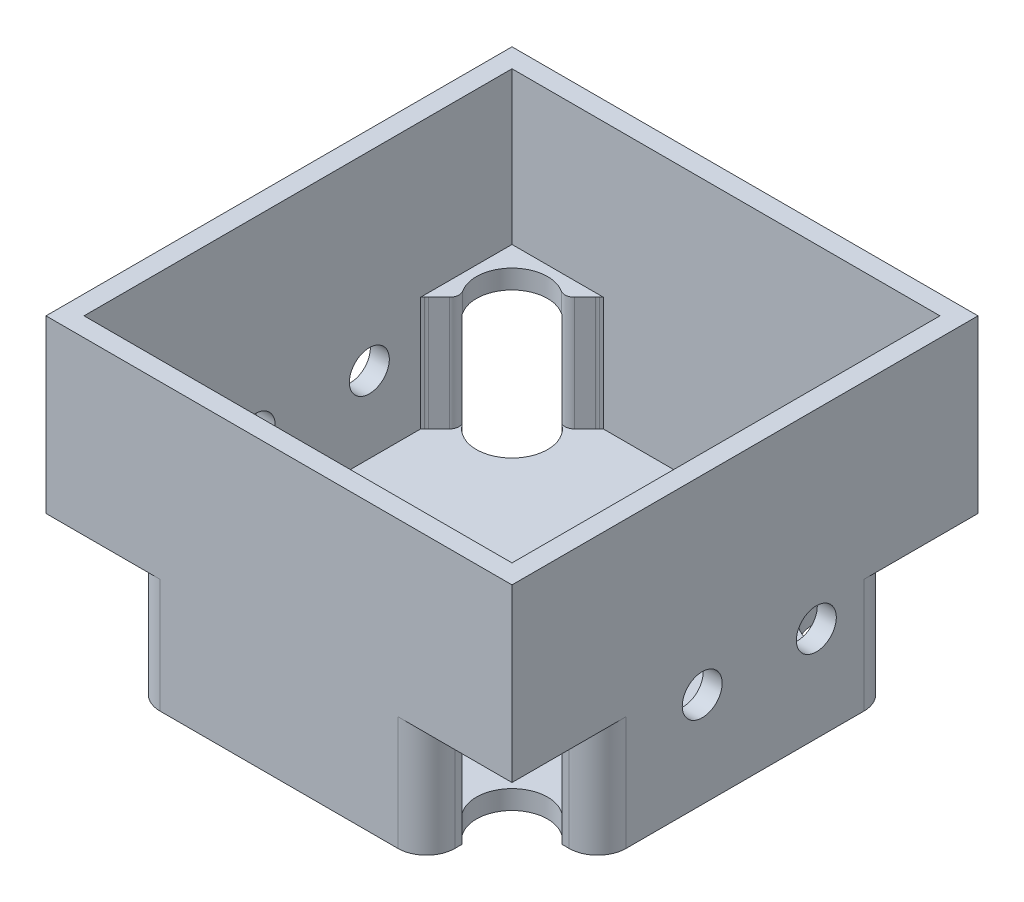
SolidWorks part; units mm, degrees
ref_plane "前视基准面" through (0, 0, 0) normal (0, 0, 1) x (1, 0, 0)
ref_plane "上视基准面" through (0, 0, 0) normal (0, 1, 0) x (1, 0, 0)
ref_plane "右视基准面" through (0, 0, 0) normal (1, 0, 0) x (0, 0, -1)
sketch "草图3" plane through (0, 0, 0) normal (0, -1, 0) x (-1, 0, 0)
  line L0 (18.5, 15.5) -> (21.5, 15.5)
  line L1 (24.5, 12.5) -> (24.5, -12.5)
  line L2 (21.5, -15.5) -> (18.5, -15.5)
  line L3 (15.5, -18.5) -> (15.5, -21.5)
  line L4 (12.5, -24.5) -> (-12.5, -24.5)
  line L5 (-15.5, -21.5) -> (-15.5, -18.5)
  line L6 (-18.5, -15.5) -> (-21.5, -15.5)
  line L7 (-24.5, -12.5) -> (-24.5, 12.5)
  line L8 (-21.5, 15.5) -> (-18.5, 15.5)
  line L9 (-15.5, 18.5) -> (-15.5, 21.5)
  line L10 (-12.5, 24.5) -> (12.5, 24.5)
  line L11 (15.5, 21.5) -> (15.5, 18.5)
  line L12 (18.5, 13.5) -> (21.5, 13.5)
  line L13 (13.5, 21.5) -> (13.5, 18.5)
  line L14 (22.5, 12.5) -> (22.5, -12.5)
  line L15 (21.5, -13.5) -> (18.5, -13.5)
  line L16 (13.5, -18.5) -> (13.5, -21.5)
  line L17 (12.5, -22.5) -> (-12.5, -22.5)
  line L18 (-13.5, -21.5) -> (-13.5, -18.5)
  line L19 (-18.5, -13.5) -> (-21.5, -13.5)
  line L20 (-22.5, -12.5) -> (-22.5, 12.5)
  line L21 (-21.5, 13.5) -> (-18.5, 13.5)
  line L22 (-13.5, 18.5) -> (-13.5, 21.5)
  line L23 (-12.5, 22.5) -> (12.5, 22.5)
  arc A0 (24.5, 12.5) -> (21.5, 15.5) centre (21.5, 12.5) ccw
  arc A1 (21.5, -15.5) -> (24.5, -12.5) centre (21.5, -12.5) ccw
  arc A2 (18.5, -15.5) -> (15.5, -18.5) centre (18.5, -18.5) ccw
  arc A3 (12.5, -24.5) -> (15.5, -21.5) centre (12.5, -21.5) ccw
  arc A4 (-15.5, -21.5) -> (-12.5, -24.5) centre (-12.5, -21.5) ccw
  arc A5 (-15.5, -18.5) -> (-18.5, -15.5) centre (-18.5, -18.5) ccw
  arc A6 (-24.5, -12.5) -> (-21.5, -15.5) centre (-21.5, -12.5) ccw
  arc A7 (-21.5, 15.5) -> (-24.5, 12.5) centre (-21.5, 12.5) ccw
  arc A8 (-18.5, 15.5) -> (-15.5, 18.5) centre (-18.5, 18.5) ccw
  arc A9 (-12.5, 24.5) -> (-15.5, 21.5) centre (-12.5, 21.5) ccw
  arc A10 (15.5, 21.5) -> (12.5, 24.5) centre (12.5, 21.5) ccw
  arc A11 (15.5, 18.5) -> (18.5, 15.5) centre (18.5, 18.5) ccw
  arc A12 (22.5, 12.5) -> (21.5, 13.5) centre (21.5, 12.5) ccw
  arc A13 (13.5, 18.5) -> (18.5, 13.5) centre (18.5, 18.5) ccw
  arc A14 (13.5, 21.5) -> (12.5, 22.5) centre (12.5, 21.5) ccw
  arc A15 (21.5, -13.5) -> (22.5, -12.5) centre (21.5, -12.5) ccw
  arc A16 (18.5, -13.5) -> (13.5, -18.5) centre (18.5, -18.5) ccw
  arc A17 (12.5, -22.5) -> (13.5, -21.5) centre (12.5, -21.5) ccw
  arc A18 (-13.5, -21.5) -> (-12.5, -22.5) centre (-12.5, -21.5) ccw
  arc A19 (-13.5, -18.5) -> (-18.5, -13.5) centre (-18.5, -18.5) ccw
  arc A20 (-22.5, -12.5) -> (-21.5, -13.5) centre (-21.5, -12.5) ccw
  arc A21 (-21.5, 13.5) -> (-22.5, 12.5) centre (-21.5, 12.5) ccw
  arc A22 (-18.5, 13.5) -> (-13.5, 18.5) centre (-18.5, 18.5) ccw
  arc A23 (-12.5, 22.5) -> (-13.5, 21.5) centre (-12.5, 21.5) ccw
  point P4 (0, 22.5)
  point P7 (22.5, 0)
  dimension "D5" = 5
  dimension "D6" = 5
  dimension "D7" = 5
  dimension "D8" = 5
  dimension "D17" = 1
  dimension "D18" = 1
  dimension "D19" = 1
  dimension "D20" = 1
  dimension "D21" = 1
  dimension "D22" = 1
  dimension "D23" = 1
  dimension "D24" = 1
  dimension "D1" = 25
  dimension "D2" = 25
  dimension "D3" = 25
  dimension "D4" = 25
  dimension "D9" = 3
  dimension "D10" = 3
  dimension "D11" = 3
  dimension "D12" = 3
  dimension "D13" = 3
  dimension "D14" = 3
  dimension "D15" = 3
  dimension "D16" = 3
  dimension "D25" = 2
extrude "凸台-拉伸1" add sketch "草图3" against normal blind 12
sketch "草图4" plane through (0, 0, 0) normal (0, -1, 0) x (1, 0, 0)
  line L0 (-24.5, 12.5) -> (-24.5, -12.5) construction
  line L1 (-21.5, -15.5) -> (-18.5, -15.5) construction
  line L2 (-15.5, -18.5) -> (-15.5, -21.5) construction
  line L3 (-12.5, -24.5) -> (12.5, -24.5) construction
  line L4 (15.5, -21.5) -> (15.5, -18.5) construction
  line L5 (18.5, -15.5) -> (21.5, -15.5) construction
  line L6 (24.5, -12.5) -> (24.5, 12.5) construction
  line L7 (21.5, 15.5) -> (18.5, 15.5) construction
  line L8 (15.5, 18.5) -> (15.5, 21.5) construction
  line L9 (12.5, 24.5) -> (-12.5, 24.5) construction
  line L10 (-15.5, 21.5) -> (-15.5, 18.5) construction
  line L11 (-18.5, 15.5) -> (-21.5, 15.5) construction
  line L12 (-24.5, 12.5) -> (-24.5, -12.5)
  line L13 (-21.5, -15.5) -> (-18.5, -15.5)
  line L14 (-15.5, -18.5) -> (-15.5, -21.5)
  line L15 (-12.5, -24.5) -> (12.5, -24.5)
  line L16 (15.5, -21.5) -> (15.5, -18.5)
  line L17 (18.5, -15.5) -> (21.5, -15.5)
  line L18 (24.5, -12.5) -> (24.5, 12.5)
  line L19 (21.5, 15.5) -> (18.5, 15.5)
  line L20 (15.5, 18.5) -> (15.5, 21.5)
  line L21 (12.5, 24.5) -> (-12.5, 24.5)
  line L22 (-15.5, 21.5) -> (-15.5, 18.5)
  line L23 (-18.5, 15.5) -> (-21.5, 15.5)
  arc A1 (-18.5, 15.5) -> (-15.5, 18.5) centre (-18.5, 18.5) ccw construction
  arc A2 (-18.5, 15.5) -> (-15.5, 18.5) centre (-18.5, 18.5) ccw
  arc A3 (-24.5, -12.5) -> (-21.5, -15.5) centre (-21.5, -12.5) ccw construction
  arc A4 (-15.5, -18.5) -> (-18.5, -15.5) centre (-18.5, -18.5) ccw construction
  arc A5 (-15.5, -21.5) -> (-12.5, -24.5) centre (-12.5, -21.5) ccw construction
  arc A6 (12.5, -24.5) -> (15.5, -21.5) centre (12.5, -21.5) ccw construction
  arc A7 (18.5, -15.5) -> (15.5, -18.5) centre (18.5, -18.5) ccw construction
  arc A8 (21.5, -15.5) -> (24.5, -12.5) centre (21.5, -12.5) ccw construction
  arc A9 (24.5, 12.5) -> (21.5, 15.5) centre (21.5, 12.5) ccw construction
  arc A10 (15.5, 18.5) -> (18.5, 15.5) centre (18.5, 18.5) ccw construction
  arc A11 (15.5, 21.5) -> (12.5, 24.5) centre (12.5, 21.5) ccw construction
  arc A12 (-12.5, 24.5) -> (-15.5, 21.5) centre (-12.5, 21.5) ccw construction
  arc A13 (-21.5, 15.5) -> (-24.5, 12.5) centre (-21.5, 12.5) ccw construction
  arc A14 (-24.5, -12.5) -> (-21.5, -15.5) centre (-21.5, -12.5) ccw
  arc A15 (-15.5, -18.5) -> (-18.5, -15.5) centre (-18.5, -18.5) ccw
  arc A16 (-15.5, -21.5) -> (-12.5, -24.5) centre (-12.5, -21.5) ccw
  arc A17 (12.5, -24.5) -> (15.5, -21.5) centre (12.5, -21.5) ccw
  arc A18 (18.5, -15.5) -> (15.5, -18.5) centre (18.5, -18.5) ccw
  arc A19 (21.5, -15.5) -> (24.5, -12.5) centre (21.5, -12.5) ccw
  arc A20 (24.5, 12.5) -> (21.5, 15.5) centre (21.5, 12.5) ccw
  arc A21 (15.5, 18.5) -> (18.5, 15.5) centre (18.5, 18.5) ccw
  arc A22 (15.5, 21.5) -> (12.5, 24.5) centre (12.5, 21.5) ccw
  arc A23 (-12.5, 24.5) -> (-15.5, 21.5) centre (-12.5, 21.5) ccw
  arc A24 (-21.5, 15.5) -> (-24.5, 12.5) centre (-21.5, 12.5) ccw
extrude "凸台-拉伸2" add sketch "草图4" along normal blind 2
sketch "草图2" plane through (0, 12, 0) normal (0, 1, 0) x (1, 0, 0)
  line L0 (-24.5, 24.5) -> (24.5, 24.5)
  line L1 (-22.5, 22.5) -> (22.5, 22.5)
  line L2 (-22.5, 22.5) -> (-22.5, -22.5)
  line L3 (-22.5, -22.5) -> (22.5, -22.5)
  line L4 (22.5, 22.5) -> (22.5, -22.5)
  line L5 (24.5, 24.5) -> (24.5, -24.5)
  line L6 (-24.5, -24.5) -> (24.5, -24.5)
  line L7 (-24.5, 24.5) -> (-24.5, -24.5)
  line L8 (-12.5, 24.5) -> (12.5, 24.5) construction
  line L9 (-24.5, -12.5) -> (-24.5, 12.5) construction
  dimension "D1" = 45
  dimension "D2" = 45
  dimension "D3" = 2
extrude "凸台-拉伸3" add sketch "草图2" along normal blind 16
sketch "草图6" plane through (0, 12, 0) normal (0, -1, 0) x (1, 0, 0)
  line L18 (12.5, 24.5) -> (24.5, 24.5)
  line L19 (24.5, 24.5) -> (24.5, 12.5)
  line L20 (21.5, 15.5) -> (18.5, 15.5)
  line L21 (15.5, 21.5) -> (15.5, 18.5)
  line L22 (-24.5, -12.5) -> (-24.5, -24.5)
  line L23 (-24.5, -24.5) -> (-12.5, -24.5)
  line L24 (-15.5, -18.5) -> (-15.5, -21.5)
  line L25 (-24.5, 12.5) -> (-24.5, 24.5)
  line L26 (-24.5, 24.5) -> (-12.5, 24.5)
  line L27 (-15.5, 21.5) -> (-15.5, 18.5)
  line L28 (-18.5, 15.5) -> (-21.5, 15.5)
  line L39 (-21.5, -15.5) -> (-18.5, -15.5)
  line L40 (12.5, -24.5) -> (24.5, -24.5)
  line L41 (24.5, -24.5) -> (24.5, -12.5)
  line L42 (18.5, -15.5) -> (21.5, -15.5)
  line L43 (15.5, -21.5) -> (15.5, -18.5)
  arc A9 (24.5, 12.5) -> (21.5, 15.5) centre (21.5, 12.5) ccw
  arc A10 (15.5, 18.5) -> (18.5, 15.5) centre (18.5, 18.5) ccw
  arc A11 (15.5, 21.5) -> (12.5, 24.5) centre (12.5, 21.5) ccw
  arc A12 (-15.5, -18.5) -> (-18.5, -15.5) centre (-18.5, -18.5) ccw
  arc A13 (-24.5, -12.5) -> (-21.5, -15.5) centre (-21.5, -12.5) ccw
  arc A14 (-12.5, 24.5) -> (-15.5, 21.5) centre (-12.5, 21.5) ccw
  arc A15 (-18.5, 15.5) -> (-15.5, 18.5) centre (-18.5, 18.5) ccw
  arc A16 (-21.5, 15.5) -> (-24.5, 12.5) centre (-21.5, 12.5) ccw
  arc A17 (-15.5, -21.5) -> (-12.5, -24.5) centre (-12.5, -21.5) ccw
  arc A20 (18.5, -15.5) -> (15.5, -18.5) centre (18.5, -18.5) ccw
  arc A26 (21.5, -15.5) -> (24.5, -12.5) centre (21.5, -12.5) ccw
  arc A27 (12.5, -24.5) -> (15.5, -21.5) centre (12.5, -21.5) ccw
extrude "凸台-拉伸4" add sketch "草图6" along normal blind 2
sketch "草图5" plane through (0, -2, 0) normal (0, -1, 0) x (1, 0, 0)
  line L8 (-22.5, -22.5) -> (-22.5, -12.5) construction
  line L11 (-22.5, 22.5) -> (-12.5, 22.5) construction
  line L12 (22.5, 22.5) -> (22.5, 12.5) construction
  line L13 (22.5, -22.5) -> (12.5, -22.5) construction
  circle A0 centre (-17.7, 17.7) radius 2.25
  circle A1 centre (-17.7, -17.7) radius 2.25
  circle A2 centre (17.7, 17.7) radius 2.25
  circle A3 centre (17.7, -17.7) radius 2.25
  dimension "D1" = 4.5
  dimension "D2" = 4.8
  dimension "D3" = 4.8
  dimension "D4" = 4.8
  dimension "D5" = 4.8
extrude "切除-拉伸2" cut sketch "草图5" against normal through all
sketch "草图7" plane through (0, -2, 0) normal (0, -1, 0) x (1, 0, 0)
  circle A0 centre (-17.7, 17.7) radius 3.75
  circle A1 centre (-17.7, -17.7) radius 3.75
  circle A2 centre (17.7, -17.7) radius 3.75
  circle A3 centre (17.7, 17.7) radius 3.75
  dimension "D1" = 7.5
extrude "切除-拉伸3" cut sketch "草图7" against normal through all
sketch "草图8" plane through (22.5, 0, 0) normal (-1, 0, 0) x (0, 0, 1)
  line L0 (-12.5, 12) -> (-12.5, 0) construction
  line L1 (-12.5, 0) -> (12.5, 0) construction
  line L2 (12.5, 12) -> (12.5, 0) construction
  circle A0 centre (-7.5, 8) radius 2.1
  circle A1 centre (4.5, 8) radius 2.1
  dimension "D2" = 4.2
  dimension "D1" = 12
  dimension "D3" = 5
  dimension "D4" = 8
  dimension "D5" = 8
extrude "切除-拉伸4" cut sketch "草图8" against normal through all both and the other way through all
sketch "草图16" plane through (0, 10, 0) normal (0, -1, 0) x (1, 0, 0)
  line L0 (24.5, 24.5) -> (12.5, 24.5) construction
  line L1 (21.5, 15.5) -> (20.7369, 15.5) construction
  line L2 (15.5, 21.5) -> (15.5, 20.7369) construction
  line L3 (21.5, 15.5) -> (20.7369, 15.5)
  line L4 (15.5, 21.5) -> (15.5, 20.7369)
  line L5 (21.5, -15.5) -> (20.7369, -15.5)
  line L6 (15.5, -21.5) -> (15.5, -20.7369)
  line L7 (-15.5, -21.5) -> (-15.5, -20.7369)
  line L8 (-21.5, -15.5) -> (-20.7369, -15.5)
  line L9 (-21.5, 15.5) -> (-20.7369, 15.5)
  line L10 (-15.5, 21.5) -> (-15.5, 20.7369)
  arc A0 (24.5, 12.5) -> (12.5, 24.5) centre (12.5, 12.5) ccw
  arc A1 (24.5, 12.5) -> (21.5, 15.5) centre (21.5, 12.5) ccw construction
  arc A2 (20.7369, 15.5) -> (15.5, 20.7369) centre (17.7, 17.7) ccw construction
  arc A3 (15.5, 21.5) -> (12.5, 24.5) centre (12.5, 21.5) ccw construction
  arc A4 (24.5, 12.5) -> (21.5, 15.5) centre (21.5, 12.5) ccw
  arc A5 (20.7369, 15.5) -> (15.5, 20.7369) centre (17.7, 17.7) ccw
  arc A6 (15.5, 21.5) -> (12.5, 24.5) centre (12.5, 21.5) ccw
  arc A7 (12.5, -24.5) -> (24.5, -12.5) centre (12.5, -12.5) ccw
  arc A8 (21.5, -15.5) -> (24.5, -12.5) centre (21.5, -12.5) ccw
  arc A9 (15.5, -20.7369) -> (20.7369, -15.5) centre (17.7, -17.7) ccw
  arc A10 (12.5, -24.5) -> (15.5, -21.5) centre (12.5, -21.5) ccw
  arc A11 (-24.5, -12.5) -> (-12.5, -24.5) centre (-12.5, -12.5) ccw
  arc A12 (-15.5, -21.5) -> (-12.5, -24.5) centre (-12.5, -21.5) ccw
  arc A13 (-20.7369, -15.5) -> (-15.5, -20.7369) centre (-17.7, -17.7) ccw
  arc A14 (-24.5, -12.5) -> (-21.5, -15.5) centre (-21.5, -12.5) ccw
  arc A15 (-12.5, 24.5) -> (-24.5, 12.5) centre (-12.5, 12.5) ccw
  arc A16 (-21.5, 15.5) -> (-24.5, 12.5) centre (-21.5, 12.5) ccw
  arc A17 (-15.5, 20.7369) -> (-20.7369, 15.5) centre (-17.7, 17.7) ccw
  arc A18 (-12.5, 24.5) -> (-15.5, 21.5) centre (-12.5, 21.5) ccw
  dimension "D1" = 4
sketch "草图15" plane through (0, 12, 0) normal (0, 1, 0) x (1, 0, 0)
  line L0 (-22.5, 12.9) -> (-22.5, -12.9)
  line L1 (-12.9, -22.5) -> (12.9, -22.5)
  line L2 (22.5, -12.9) -> (22.5, 12.9)
  line L3 (12.9, 22.5) -> (-12.9, 22.5)
  line L4 (-17.7, 17.7) -> (-12.9, 22.5)
  line L5 (-17.7, 17.7) -> (-22.5, 12.9)
  line L6 (17.7, 17.7) -> (22.5, 12.9)
  line L7 (17.7, 17.7) -> (12.9, 22.5)
  line L8 (17.7, -17.7) -> (12.9, -22.5)
  line L9 (17.7, -17.7) -> (22.5, -12.9)
  line L10 (-17.7, -17.7) -> (-22.5, -12.9)
  line L11 (-17.7, -17.7) -> (-12.9, -22.5)
  dimension "D1" = 45
  dimension "D2" = 4
extrude "切除-拉伸10" cut sketch "草图15" against normal up to surface (12 mm away) up to face at (0, 0, 0)
sketch "草图17" plane through (0, 0, 0) normal (0, 1, 0) x (1, 0, 0)
  circle A0 centre (-17.7, 17.7) radius 3.75
  circle A1 centre (17.7, 17.7) radius 3.75
fillet "圆角2" radius 1 8 edges at (20.3517, 6, -15.0483) (15.0483, 6, -20.3517) (20.3517, 6, 15.0483) (15.0483, 6, 20.3517) (-15.0483, 6, 20.3517) (-20.3517, 6, 15.0483) (-20.3517, 6, -15.0483) (-15.0483, 6, -20.3517)
